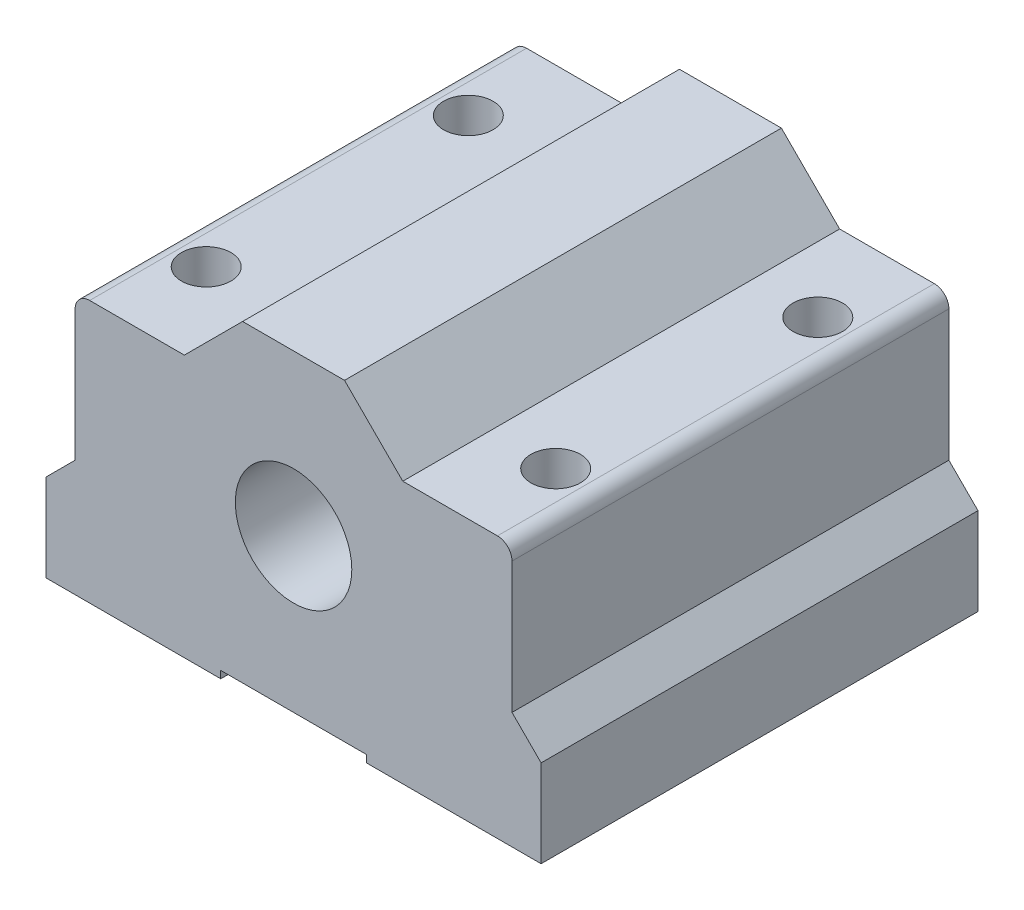
SolidWorks part; units mm, degrees
ref_plane "前视基准面" through (0, 0, 0) normal (0, 0, 1) x (1, 0, 0)
ref_plane "上视基准面" through (0, 0, 0) normal (0, 1, 0) x (1, 0, 0)
ref_plane "右视基准面" through (0, 0, 0) normal (1, 0, 0) x (0, 0, -1)
sketch "草图1" plane through (0, 0, 0) normal (0, 0, 1) x (1, 0, 0)
  line L1 (0, 0) -> (34, 0)
  line L2 (0, 0) -> (0, 22)
  line L3 (0, 22) -> (34, 22)
  line L4 (34, 0) -> (34, 22)
  dimension "D1" = 22
  dimension "D2" = 34
extrude "凸台-拉伸1" add sketch "草图1" along normal blind 30
sketch "草图2" plane through (0, 0, 30) normal (0, 0, 1) x (1, 0, 0)
  line L0 (0, 11) -> (34, 11) construction
  line L1 (0, 22) -> (0, 0) construction
  line L2 (34, 0) -> (34, 22) construction
  line L3 (17, 22) -> (17, 0) construction
  line L4 (34, 22) -> (0, 22) construction
  line L5 (0, 0) -> (34, 0) construction
  line L6 (0, 18) -> (9.5, 18)
  line L7 (9.5, 18) -> (13.5, 22)
  line L8 (24.5, 18) -> (20.5, 22)
  line L9 (34, 18) -> (24.5, 18)
  circle A0 centre (17, 11) radius 4
  point P20 (0, 0)
  point P21 (0, 0)
  line M4 (0, 22) -> (0, 0)
  line M6 (34, 0) -> (34, 22)
  line M7 (34, 22) -> (0, 22)
  dimension "D1" = 8
  dimension "D2" = 18
  dimension "D3" = 15
  dimension "D4" = 135
extrude "切除-拉伸1" cut sketch "草图2" against normal through all contours L6 L7 M7 M4 | L9 L8 M6 M7 | A0
sketch "草图3" plane through (0, 0, 30) normal (0, 0, 1) x (1, 0, 0)
  line L0 (0, 6) -> (2, 8)
  line L1 (0, 18) -> (0, 0) construction
  line L2 (2, 8) -> (2, 18)
  line L3 (0, 18) -> (9.5, 18) construction
  line L4 (17, 22) -> (17, 0) construction
  line L5 (20.5, 22) -> (13.5, 22) construction
  line L6 (0, 0) -> (34, 0) construction
  line L7 (12, 0) -> (12, 0.5)
  line L8 (12, 0.5) -> (22, 0.5)
  line L9 (22, 0) -> (22, 0.5)
  line L10 (34, 6) -> (32, 8)
  line L11 (32, 8) -> (32, 18)
  line L12 (2, 18) -> (0, 18)
  line L13 (0, 18) -> (0, 6)
  line L14 (32, 18) -> (34, 18)
  line L15 (34, 18) -> (34, 6)
  line L16 (12, 0) -> (22, 0)
  point P17 (12, 0.25)
  point P20 (17, 0.5)
  dimension "D1" = 135
  dimension "D2" = 6
  dimension "D3" = 8
  dimension "D4" = 5
  dimension "D5" = 0.5
extrude "切除-拉伸2" cut sketch "草图3" against normal through all
fillet "圆角1" radius 1 2 edges at (32, 18, 15) (2, 18, 15)
sketch "草图4" plane through (0, 0, 0) normal (0, -1, 0) x (1, 0, 0)
  line L0 (0, 15) -> (34, 15) construction
  line L1 (0, 30) -> (0, 0) construction
  line L2 (34, 30) -> (34, 0) construction
  line L3 (17, 12.5) -> (17, 29.872) construction
  circle A0 centre (5, 24) radius 1.7
  circle A1 centre (29, 24) radius 1.7
  circle A2 centre (5, 6) radius 1.7
  circle A3 centre (29, 6) radius 1.7
  point P7 (17, 15)
  dimension "D3" = 3.4
  dimension "D1" = 18
  dimension "D2" = 24
extrude "切除-拉伸3" cut sketch "草图4" against normal through all
thread "螺纹线1" pitch 0.7 start angle 0, offset 0, length 8, pitch 0.7, diameter 3.4
ref_plane "基准面1" through (6.7, 0, 24) normal (0, 0, 1) x (1, 0, 0)
sketch "螺纹线轮廓1" plane through (6.7, 0, 24) normal (0, 0, 1) x (1, 0, 0)
  line L0 (0, 0) -> (0, 0.7) construction
  line L11 (0, 0) -> (0, 0.6125)
  line L12 (0, 0.6125) -> (-0.3789, 0.3937)
  line L13 (-0.3789, 0.3937) -> (-0.3789, 0.2187)
  line L15 (-0.3789, 0.2187) -> (0, 0)
  line L17 (-0.3789, 0.3062) -> (0, 0.3062) construction
  point P2 (0, 0)
  dimension "Pitch" = 0.7
  dimension "Profile_Angle" = 60
  dimension "Profile_Land" = 0.175
  dimension "Profile_Height" = 0.3789
thread "螺纹线2" pitch 0.7 profile "螺纹线轮廓2" start angle 0, offset 0, length 8, pitch 0.7, diameter 3.4
ref_plane "基准面2" through (6.7, 0, 6) normal (0, 0, 1) x (1, 0, 0)
sketch "螺纹线轮廓2" plane through (6.7, 0, 6) normal (0, 0, 1) x (1, 0, 0)
  line L0 (0, 0) -> (0, 0.7) construction
  line L11 (0, 0) -> (0, 0.6125)
  line L12 (0, 0.6125) -> (-0.3789, 0.3937)
  line L13 (-0.3789, 0.3937) -> (-0.3789, 0.2187)
  line L15 (-0.3789, 0.2187) -> (0, 0)
  line L17 (-0.3789, 0.3062) -> (0, 0.3062) construction
  point P2 (0, 0)
  dimension "Pitch" = 0.7
  dimension "Profile_Angle" = 60
  dimension "Profile_Land" = 0.175
  dimension "Profile_Height" = 0.3789
thread "螺纹线3" pitch 0.7 profile "螺纹线轮廓3" start angle 0, offset 0, length 8, pitch 0.7, diameter 3.4
ref_plane "基准面3" through (30.7, 0, 24) normal (0, 0, 1) x (1, 0, 0)
sketch "螺纹线轮廓3" plane through (30.7, 0, 24) normal (0, 0, 1) x (1, 0, 0)
  line L0 (0, 0) -> (0, 0.7) construction
  line L11 (0, 0) -> (0, 0.6125)
  line L12 (0, 0.6125) -> (-0.3789, 0.3937)
  line L13 (-0.3789, 0.3937) -> (-0.3789, 0.2187)
  line L15 (-0.3789, 0.2187) -> (0, 0)
  line L17 (-0.3789, 0.3062) -> (0, 0.3062) construction
  point P2 (0, 0)
  dimension "Pitch" = 0.7
  dimension "Profile_Angle" = 60
  dimension "Profile_Land" = 0.175
  dimension "Profile_Height" = 0.3789
thread "螺纹线4" pitch 0.7 profile "螺纹线轮廓4" start angle 0, offset 0, length 8, pitch 0.7, diameter 3.4
ref_plane "基准面4" through (30.7, 0, 6) normal (0, 0, 1) x (1, 0, 0)
sketch "螺纹线轮廓4" plane through (30.7, 0, 6) normal (0, 0, 1) x (1, 0, 0)
  line L0 (0, 0) -> (0, 0.7) construction
  line L11 (0, 0) -> (0, 0.6125)
  line L12 (0, 0.6125) -> (-0.3789, 0.3937)
  line L13 (-0.3789, 0.3937) -> (-0.3789, 0.2187)
  line L15 (-0.3789, 0.2187) -> (0, 0)
  line L17 (-0.3789, 0.3062) -> (0, 0.3062) construction
  point P2 (0, 0)
  dimension "Pitch" = 0.7
  dimension "Profile_Angle" = 60
  dimension "Profile_Land" = 0.175
  dimension "Profile_Height" = 0.3789
